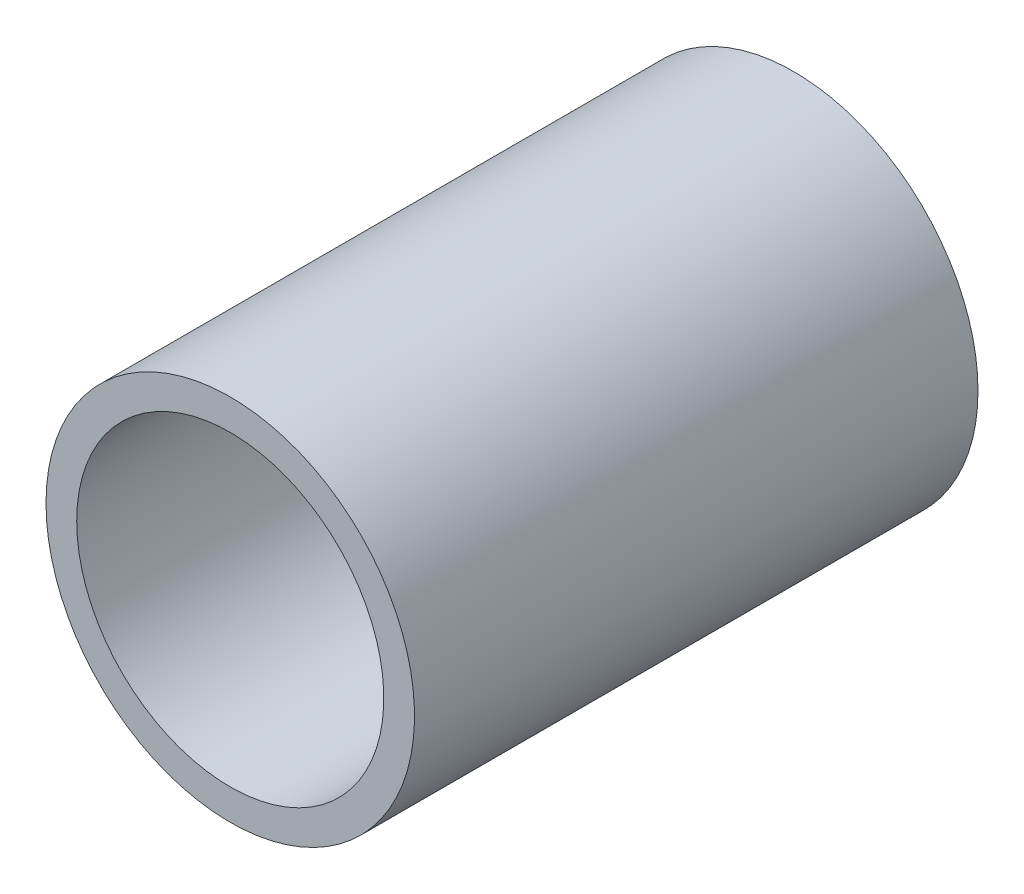
SolidWorks part; units mm, degrees
material "PLA 50%"
ref_plane "Front Plane" through (0, 0, 0) normal (0, 0, 1) x (1, 0, 0)
ref_plane "Top Plane" through (0, 0, 0) normal (0, 1, 0) x (1, 0, 0)
ref_plane "Right Plane" through (0, 0, 0) normal (1, 0, 0) x (0, 0, -1)
ref_axis "X" through (-88.99, 0, 0) along (1, 0, 0)
ref_axis "Y" through (0, 55, 0) along (0, -1, 0)
ref_axis "Z" through (0, 0, -88.99) along (0, 0, 1)
sketch "Sketch1" plane through (0, 0, 0) normal (0, 0, 1) x (1, 0, 0)
  circle A0 centre (0, 0) radius 5
  circle A1 centre (0, 0) radius 6
  dimension "D1" = 10
  dimension "D2" = 12
extrude "Boss-Extrude1" add sketch "Sketch1" along normal up to surface (18.3488 mm away)
